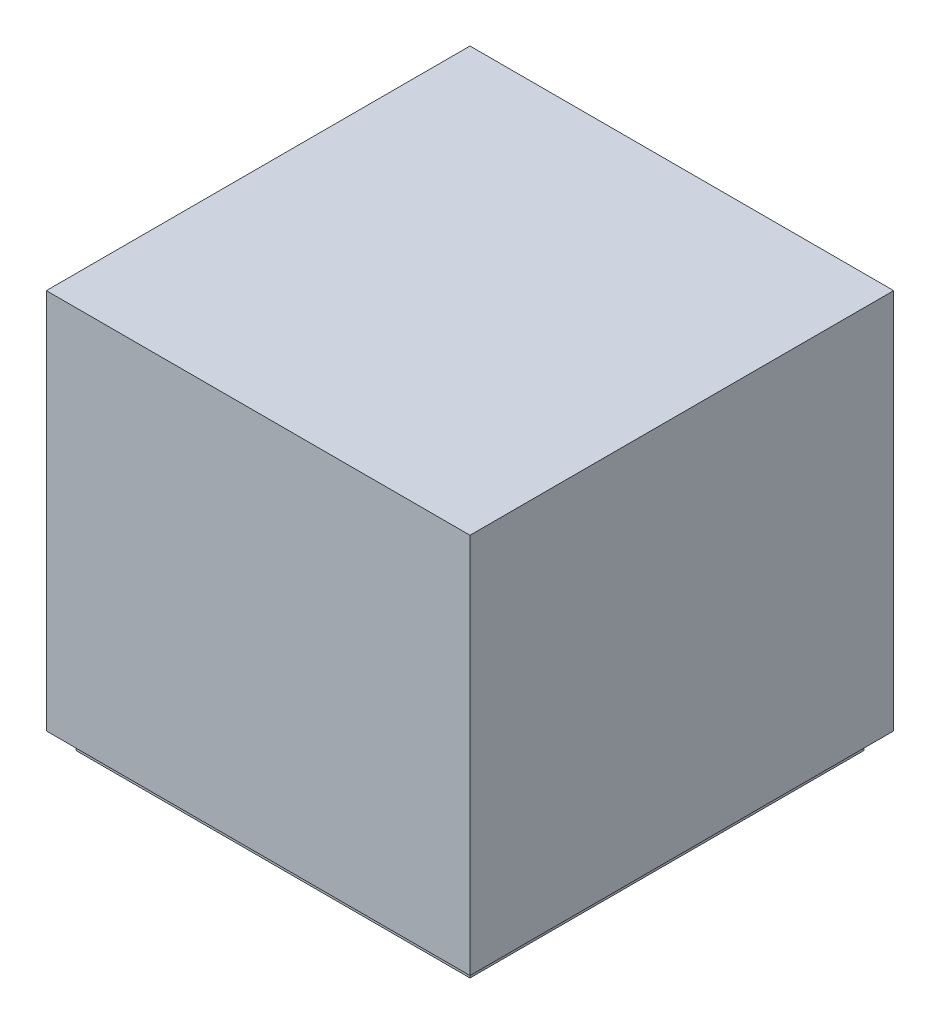
SolidWorks part; units mm, degrees
ref_plane "Front Plane" through (0, 0, 0) normal (0, 0, 1) x (1, 0, 0)
ref_plane "Top Plane" through (0, 0, 0) normal (0, 1, 0) x (1, 0, 0)
ref_plane "Right Plane" through (0, 0, 0) normal (1, 0, 0) x (0, 0, -1)
sketch "Sketch1" plane through (0, 0, 0) normal (0, 1, 0) x (1, 0, 0)
  line L1 (-465, -465) -> (465, -465)
  line L2 (-465, -465) -> (-465, 465)
  line L3 (-465, 465) -> (465, 465)
  line L4 (465, -465) -> (465, 465)
  line L5 (-465, -465) -> (465, 465) construction
  line L6 (-465, 465) -> (465, -465) construction
  line L7 (500, 500) -> (-500, 500)
  line L8 (500, 500) -> (500, -500)
  line L9 (500, -500) -> (-500, -500)
  line L10 (-500, 500) -> (-500, -500)
  line L11 (500, 500) -> (-500, -500) construction
  line L12 (500, -500) -> (-500, 500) construction
  line L13 (-425, -425) -> (425, -425)
  line L14 (-425, -425) -> (-425, 425)
  line L15 (-425, 425) -> (425, 425)
  line L16 (425, -425) -> (425, 425)
  line L17 (-425, -425) -> (425, 425) construction
  line L18 (-425, 425) -> (425, -425) construction
  point P0 (0, 0)
  point P6 (0, 0)
  point P11 (0, 0)
  dimension "D1" = 930
  dimension "D2" = 1000
  dimension "D3" = 850
extrude "Boss-Extrude2" add sketch "Sketch1" along normal blind 900 contours L1 L4 L3 L2 L16 L13 L14 L15 | L7 L10 L9 L8 L4 L1 L2 L3 region at (-451.8478, 0, 0) region at (485.8579, 0, 0)
extrude "Boss-Extrude3" add sketch "Sketch1<4>" against normal blind 40 contours L1 L4 L3 L2 L16 L13 L14 L15 region at (-451.8478, 0, 0)
sketch "Sketch1<4>" plane through (0, 0, 0) normal (0, 1, 0) x (1, 0, 0) same geometry as "Sketch1"
extrude "Boss-Extrude4" add sketch "Sketch1<5>" against normal blind 2 from surface contours L13 L16 L15 L14 region at (0, 0, 0) starting at face at (0, 900, 0)
sketch "Sketch1<5>" plane through (0, 0, 0) normal (0, 1, 0) x (1, 0, 0) same geometry as "Sketch1"
